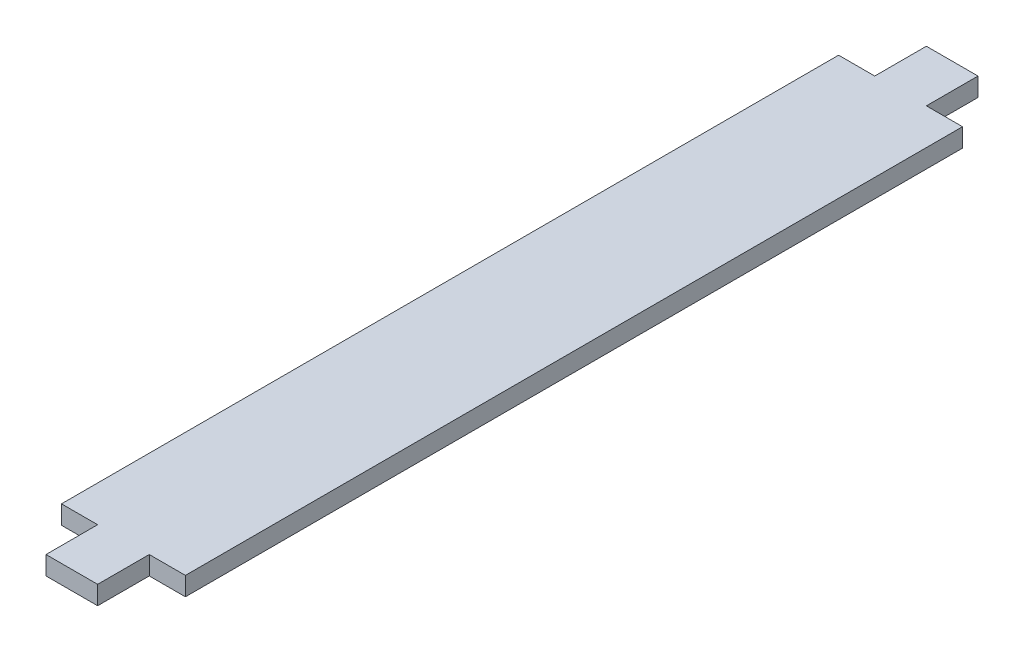
SolidWorks part; units mm, degrees
ref_plane "Front Plane" through (0, 0, 0) normal (0, 0, 1) x (1, 0, 0)
ref_plane "Top Plane" through (0, 0, 0) normal (0, 1, 0) x (1, 0, 0)
ref_plane "Right Plane" through (0, 0, 0) normal (1, 0, 0) x (0, 0, -1)
sketch "Sketch1" plane through (0, 0, 0) normal (0, 1, 0) x (1, 0, 0)
  line L0 (-363.1089, 480) -> (-363.1089, -480)
  line L1 (-363.1089, -480) -> (-303.1089, -480)
  line L2 (-303.1089, -480) -> (-303.1089, -400)
  line L3 (-303.1089, -400) -> (303.1089, -50)
  line L4 (303.1089, -50) -> (1036.8911, -50)
  line L5 (1036.8911, -50) -> (1036.8911, 50) construction
  line L6 (1036.8911, 50) -> (303.1089, 50)
  line L7 (303.1089, 50) -> (-303.1089, 400)
  line L8 (-303.1089, 400) -> (-303.1089, 480)
  line L9 (-303.1089, 480) -> (-363.1089, 480)
  line L10 (-363.1089, 0) -> (1036.8911, 0) construction
  line L11 (0, 225) -> (0, -225) construction
  line L14 (1036.8911, 50) -> (1066.8911, 50)
  line L15 (1036.8911, 50) -> (1036.8911, -50) construction
  line L16 (1036.8911, -50) -> (1066.8911, -50)
  line L17 (1066.8911, 50) -> (1066.8911, -50)
  dimension "D1" = 960
  dimension "D2" = 60
  dimension "D3" = 100
  dimension "D4" = 1400
  dimension "D5" = 150
  dimension "D6" = 80
  dimension "D7" = 30
extrude "Boss-Extrude1" add sketch "Sketch1" along normal blind 9
sketch "Sketch2" plane through (0, 9, 0) normal (0, 1, 0) x (1, 0, 0)
  line L1 (-363.1089, 480) -> (-303.1089, 480)
  line L2 (-363.1089, 480) -> (-363.1089, 400)
  line L3 (-363.1089, 400) -> (-303.1089, 400)
  line L4 (-303.1089, 480) -> (-303.1089, 400)
  line L5 (-363.1089, -480) -> (-303.1089, -480)
  line L6 (-363.1089, -480) -> (-363.1089, -400)
  line L7 (-363.1089, -400) -> (-303.1089, -400)
  line L8 (-303.1089, -480) -> (-303.1089, -400)
extrude "Boss-Extrude2" add sketch "Sketch2" along normal blind 500
sketch "Sketch3" plane through (0, 0, 0) normal (0, 0, 1) x (1, 0, 0)
  line L0 (-333.1089, 509) -> (-333.1089, 254.2) construction
  line L1 (-363.1089, 509) -> (-303.1089, 509) construction
  line L2 (-333.1089, 254.2) -> (-333.1089, 25) construction
  line L3 (-333.1089, 25) -> (-333.1089, 0) construction
  line L4 (-363.1089, 0) -> (-303.1089, 0) construction
  line L6 (-363.1089, 509) -> (-303.1089, 509)
  line L7 (-363.1089, 509) -> (-363.1089, 9)
  line L8 (-363.1089, 9) -> (-303.1089, 9)
  line L9 (-303.1089, 509) -> (-303.1089, 9)
  circle A0 centre (-333.1089, 254.2) radius 229.2
  circle A1 centre (-333.1089, 254.2) radius 6
  circle A2 centre (-333.1089, 254.2) radius 30
  dimension "D1" = 458.4
  dimension "D3" = 12
  dimension "D2" = 25
extrude "Cut-Extrude1" cut sketch "Sketch3" against normal through all both and the other way through all contours A2 L9 A0 L7 | A0 L9 L6 L7 | A1 region at (-333.1089, 495.8654, 0) region at (-333.1089, 380.1444, 0) region at (-333.1089, 254.2, 0)
sketch "Sketch4" plane through (0, 9, 0) normal (0, 1, 0) x (1, 0, 0)
  line L0 (866.8911, 25) -> (1066.8911, 25)
  line L2 (866.8911, -25) -> (1066.8911, -25)
  line L3 (1066.8911, -25) -> (1066.8911, 25)
  line L4 (866.8911, 0) -> (1066.8911, 0) construction
  line L5 (1066.8911, -50) -> (1066.8911, 50) construction
  circle A0 centre (866.8911, 0) radius 25
  dimension "D1" = 50
  dimension "D2" = 200
extrude "Cut-Extrude2" cut sketch "Sketch4" against normal through all contours L4 A0 L2 | A0 L4 L3 L0 | A0 region at (976.6223, 9, -12.7057) region at (884.0688, 9, -17.1777) region at (976.6223, 9, 12.7057)
sketch "Sketch16" plane through (0, 0, 0) normal (0, 0, 1) x (1, 0, 0)
  line L0 (-359.656, 240.2268) -> (-348.1089, 218.2888)
  line L5 (-348.1089, 218.2888) -> (-348.1089, 24)
  line L7 (-363.1089, 9) -> (-288.1089, 9)
  line L8 (303.1089, 9) -> (-303.1089, 9) construction
  line L9 (-303.1089, 254.2) -> (-303.1089, 24)
  line L10 (-348.1089, 24) -> (-363.1089, 9)
  line L11 (-303.1089, 254.2) -> (-303.1089, 9) construction
  line L12 (-303.1089, 24) -> (-288.1089, 9)
  line L13 (-348.1089, 24) -> (-303.1089, 24) construction
  line L14 (-346.3825, 247.2134) -> (-358.4836, 270.2039)
  line L15 (-319.8353, 261.1866) -> (-331.9364, 284.1771)
  circle A0 centre (-333.1089, 254.2) radius 15
  circle A1 centre (-333.1089, 254.2) radius 30
  arc A2 (-303.1089, 254.2) -> (-363.1089, 254.2) centre (-333.1089, 254.2) ccw construction
  circle A3 centre (-360.6089, 215.2) radius 12.5 construction
  dimension "D1" = 30
  dimension "D4" = 25
  dimension "D2" = 45
  dimension "D3" = 45
extrude "Boss-Extrude8" add sketch "Sketch16" along normal blind 305 and the other way blind 305 contours A1 L0 L5 L10 L7 L12 L9 | A1 L15 A0 L14 region at (-325.4564, 117.1914, 0) region at (-362.2383, 255.3393, 0)
sketch "Sketch17" plane through (0, 0, 0) normal (1, 0, 0) x (0, 0, -1)
  line L1 (230, 309) -> (-230, 309)
  line L2 (230, 309) -> (230, 9)
  line L3 (230, 9) -> (-230, 9)
  line L4 (-230, 309) -> (-230, 9)
  line L5 (0, 0) -> (0, 309) construction
  line L6 (480, 0) -> (-480, 0) construction
  dimension "D1" = 460
  dimension "D2" = 9
  dimension "D3" = 300
extrude "Cut-Extrude9" cut sketch "Sketch17" against normal through all
sketch "Sketch7" plane through (0, 0, 0) normal (1, 0, 0) x (0, 0, -1)
  line L1 (480, 284.2) -> (230, 284.2)
  line L2 (480, 284.2) -> (480, 9)
  line L3 (480, 9) -> (230, 9)
  line L4 (230, 284.2) -> (230, 9)
  line L5 (230, 218.2888) -> (230, 24) construction
  line L6 (471, 146.6) -> (444.5, 146.6) construction
  line L7 (480, 284.2) -> (471, 284.2)
  line L8 (480, 284.2) -> (480, 9)
  line L9 (480, 9) -> (471, 9)
  line L10 (471, 284.2) -> (471, 9)
  line L11 (400, 9) -> (409, 9)
  line L12 (400, 9) -> (400, 284.2)
  line L13 (400, 284.2) -> (409, 284.2)
  line L14 (409, 9) -> (409, 284.2)
  line L15 (444.5, 284.2) -> (435.5, 284.2)
  line L16 (444.5, 284.2) -> (444.5, 9)
  line L17 (444.5, 9) -> (435.5, 9)
  line L18 (435.5, 284.2) -> (435.5, 9)
  line L19 (444.5, 146.6) -> (435.5, 146.6) construction
  line L20 (435.5, 146.6) -> (409, 146.6) construction
  line L22 (0, 274.5241) -> (0, -136.9768) construction
  line L23 (-435.5, 146.6) -> (-409, 146.6) construction
  line L24 (305, 284.2) -> (296, 284.2)
  line L25 (305, 284.2) -> (305, 9)
  line L26 (305, 9) -> (296, 9)
  line L27 (296, 284.2) -> (296, 9)
  line L28 (239, 9) -> (230, 9)
  line L29 (239, 9) -> (239, 284.2)
  line L30 (239, 284.2) -> (230, 284.2)
  line L31 (230, 9) -> (230, 284.2)
  line L32 (-444.5, 146.6) -> (-435.5, 146.6) construction
  line L33 (-471, 146.6) -> (-444.5, 146.6) construction
  line L34 (-230, 9) -> (-230, 284.2)
  line L35 (-239, 284.2) -> (-230, 284.2)
  line L36 (-239, 9) -> (-239, 284.2)
  line L37 (-239, 9) -> (-230, 9)
  line L38 (-296, 284.2) -> (-296, 9)
  line L39 (-305, 9) -> (-296, 9)
  line L40 (-305, 284.2) -> (-305, 9)
  line L41 (-305, 284.2) -> (-296, 284.2)
  line L42 (-435.5, 284.2) -> (-435.5, 9)
  line L43 (-444.5, 9) -> (-435.5, 9)
  line L44 (-444.5, 284.2) -> (-444.5, 9)
  line L45 (-444.5, 284.2) -> (-435.5, 284.2)
  line L46 (-409, 9) -> (-409, 284.2)
  line L47 (-400, 284.2) -> (-409, 284.2)
  line L48 (-400, 9) -> (-400, 284.2)
  line L49 (-400, 9) -> (-409, 9)
  line L50 (-471, 284.2) -> (-471, 9)
  line L51 (-480, 9) -> (-471, 9)
  line L52 (-480, 284.2) -> (-480, 9)
  line L53 (-480, 284.2) -> (-471, 284.2)
  line L54 (-230, 284.2) -> (-230, 9)
  line L55 (-480, 9) -> (-230, 9)
  line L56 (-480, 284.2) -> (-480, 9)
  line L57 (-480, 284.2) -> (-230, 284.2)
  line L58 (305, 218.2888) -> (305, 24) construction
  dimension "D1" = 9
  dimension "D2" = 9
  dimension "D3" = 9
  dimension "D4" = 9
  dimension "D5" = 9
extrude "Cut-Extrude4" cut sketch "Sketch7" against normal through all both and the other way through all contours L1 L16 L3 L10 | L18 L1 L14 L3 | L29 L3 L27 L1 | L57 L38 L55 L36 | L57 L42 L55 L46 | L57 L50 L55 L44 | L1 L18 L3 L16 | L45 L44 L43 L42 region at (0, 146.6, -457.75) region at (0, 146.6, -440) region at (0, 146.6, -422.25) region at (0, 146.6, -267.5) region at (0, 146.6, 267.5) region at (0, 146.6, 422.25) region at (0, 146.6, 440) region at (0, 146.6, 457.75)
sketch "Sketch10" plane through (0, 9, 0) normal (0, 1, 0) x (1, 0, 0)
  line L0 (-363.1089, 221) -> (-113.0718, 221)
  line L2 (-113.0718, 221) -> (269.7114, 0)
  line L3 (269.7114, 0) -> (-113.0718, -221)
  line L4 (-113.0718, -221) -> (-363.1089, -221)
  line L5 (-363.1089, -221) -> (-363.1089, 221)
  line L6 (0, 0) -> (269.7114, 0) construction
  line L7 (-363.1089, 0) -> (0, 0) construction
  line L8 (-113.0718, -221) -> (-113.0718, 221) construction
  line L9 (303.1089, 50) -> (-303.1089, 400) construction
  line L10 (-363.1089, -230) -> (-363.1089, 230) construction
  line L11 (303.1089, 50) -> (337.7499, 30)
  line L12 (337.7499, 30) -> (806.8911, 30)
  line L13 (806.8911, 30) -> (841.5321, 50)
  line L14 (1066.8911, 50) -> (303.1089, 50) construction
  line L15 (841.5321, 50) -> (303.1089, 50)
  line L16 (303.1089, -50) -> (337.7499, -30)
  line L17 (337.7499, -30) -> (806.8911, -30)
  line L18 (806.8911, -30) -> (841.5321, -50)
  line L19 (303.1089, -50) -> (1066.8911, -50) construction
  line L20 (841.5321, -50) -> (303.1089, -50)
  line L21 (337.7499, -30) -> (337.7499, 30) construction
  line L22 (269.7114, 0) -> (337.7499, 0) construction
  line L23 (806.8911, 30) -> (806.8911, -30) construction
  line L24 (-303.1089, -400) -> (303.1089, -50) construction
  line L25 (841.5321, 50) -> (841.5321, -50) construction
  line L27 (-363.1089, 230) -> (-288.1089, 230) construction
  line L28 (-363.1089, -230) -> (-288.1089, -230) construction
  arc A0 (866.8911, 25) -> (866.8911, -25) centre (866.8911, 0) ccw construction
  dimension "D1" = 60
  dimension "D2" = 30
  dimension "D3" = 60
  dimension "D4" = 60
  dimension "D5" = 9
  dimension "D6" = 9
extrude "Cut-Extrude6" cut sketch "Sketch10" against normal through all
sketch "Sketch11" plane through (-363.1089, 0, 0) normal (-1, 0, 0) x (0, 0, 1)
  line L0 (-480, 254.2) -> (-480, 0) construction
  line L1 (-480, 224.2) -> (-400, 224.2)
  line L2 (-480, 224.2) -> (-480, 215.2)
  line L3 (-480, 215.2) -> (-400, 215.2)
  line L4 (-400, 224.2) -> (-400, 215.2)
  line L5 (-400, 254.2) -> (-400, 9) construction
  line L6 (400, 254.2) -> (400, 9) construction
  line L7 (400, 224.2) -> (480, 224.2)
  line L8 (400, 224.2) -> (400, 215.2)
  line L9 (400, 215.2) -> (480, 215.2)
  line L10 (480, 224.2) -> (480, 215.2)
  line L11 (480, 254.2) -> (480, 0) construction
  line L12 (-400, 224.2) -> (400, 224.2) construction
  line L13 (400, 215.2) -> (-400, 215.2) construction
  line L14 (-400, 284.2) -> (-409, 284.2) construction
  dimension "D1" = 9
  dimension "D2" = 60
extrude "Boss-Extrude5" add sketch "Sketch11" against normal up to surface (60 mm away) up to face at (-303.1089, 115.9778, 435.5556)
sketch "Sketch18" plane through (-348.1089, 0, 0) normal (-1, 0, 0) x (0, 0, 1)
  line L0 (-230, 218.2888) -> (-230, 24) construction
  line L1 (-305, 218.2888) -> (-230, 218.2888)
  line L2 (-305, 218.2888) -> (-305, 209.2888)
  line L3 (-305, 209.2888) -> (-230, 209.2888)
  line L4 (-230, 218.2888) -> (-230, 209.2888)
  line L5 (230, 24) -> (230, 218.2888) construction
  line L6 (305, 218.2888) -> (230, 218.2888)
  line L7 (305, 218.2888) -> (305, 209.2888)
  line L8 (305, 209.2888) -> (230, 209.2888)
  line L9 (230, 218.2888) -> (230, 209.2888)
  dimension "D1" = 9
  dimension "D2" = 9
extrude "Boss-Extrude9" add sketch "Sketch18" against normal up to surface (45 mm away) up to face at (-303.1089, 139.1, -234.5)
sketch "Sketch12" plane through (0, 9, 0) normal (0, 1, 0) x (1, 0, 0)
  line L0 (-363.1089, -480) -> (-303.1089, -480) construction
  line L1 (-363.1089, 480) -> (-303.1089, 480)
  line L2 (-363.1089, 480) -> (-363.1089, 489)
  line L3 (-363.1089, 489) -> (-303.1089, 489)
  line L4 (-303.1089, 480) -> (-303.1089, 489)
  line L5 (-363.1089, -480) -> (-303.1089, -480)
  line L6 (-363.1089, -480) -> (-363.1089, -489)
  line L7 (-363.1089, -489) -> (-303.1089, -489)
  line L8 (-303.1089, -480) -> (-303.1089, -489)
  dimension "D1" = 9
  dimension "D2" = 9
extrude "Boss-Extrude6" add sketch "Sketch12" against normal blind 9
fillet "Fillet3" radius 9 27 edges at (-303.1089, 4.5, -489) (-363.1089, 4.5, -489) (-363.1089, 4.5, -221) (-363.1089, 4.5, 221) (-363.1089, 4.5, 489) (-303.1089, 4.5, 489) (841.5321, 4.5, 50) (806.8911, 4.5, 30) (841.5321, 4.5, -50) (806.8911, 4.5, -30) (337.7499, 4.5, -30) (337.7499, 4.5, 30) (269.7114, 4.5, 0) (-113.0718, 4.5, 221) (-113.0718, 4.5, -221) (-303.1089, 24, -234.5) (-303.1089, 24, -300.5) (-303.1089, 24, 234.5) (-303.1089, 24, 300.5) (-348.1089, 24, 234.5) (-348.1089, 24, 300.5) (-348.1089, 24, -234.5) (-348.1089, 24, -300.5) (1066.8911, 4.5, 50) (1066.8911, 4.5, 25) (1066.8911, 4.5, -25) (1066.8911, 4.5, -50)
sketch "Sketch15" plane through (0, 9, 0) normal (0, 1, 0) x (1, 0, 0)
  line L0 (-83.154, 230) -> (-83.154, -230)
  line L1 (-113.154, 230) -> (-113.154, 220.6933) construction
  line L2 (-363.1089, 230) -> (-288.1089, 230) construction
  line L4 (-83.154, -230) -> (-143.154, -230)
  line L5 (-143.154, -230) -> (-143.154, 230)
  line L6 (-143.154, 230) -> (-83.154, 230)
  line L7 (0, 0) -> (-83.154, 0) construction
  arc A0 (-110.9833, 219.7942) -> (-115.4833, 221) centre (-115.4833, 212) ccw construction
  dimension "D1" = 60
extrude "Boss-Extrude7" add sketch "Sketch15" against normal blind 9
fillet "Fillet4" radius 9 4 edges at (-83.154, 4.5, -203.7269) (-83.154, 4.5, 203.7269) (-143.154, 4.5, 221) (-143.154, 4.5, -221)
sketch "Sketch20" plane through (0, 9, 0) normal (0, 1, 0) x (1, 0, 0)
  line L0 (-348.1089, 480) -> (-348.1089, 400)
  line L1 (-363.1089, 480) -> (-303.1089, 480)
  line L2 (-363.1089, 480) -> (-363.1089, 471)
  line L3 (-363.1089, 471) -> (-303.1089, 471)
  line L4 (-303.1089, 480) -> (-303.1089, 471)
  line L5 (-363.1089, 409) -> (-303.1089, 409)
  line L6 (-363.1089, 409) -> (-363.1089, 400)
  line L7 (-363.1089, 400) -> (-303.1089, 400)
  line L8 (-303.1089, 409) -> (-303.1089, 400)
  line L9 (-363.1089, 305) -> (-288.1089, 305)
  line L10 (-363.1089, 305) -> (-363.1089, 296)
  line L11 (-363.1089, 296) -> (-288.1089, 296)
  line L12 (-288.1089, 305) -> (-288.1089, 296)
  line L13 (-363.1089, 239) -> (-288.1089, 239)
  line L14 (-363.1089, 239) -> (-363.1089, 230)
  line L15 (-363.1089, 230) -> (-288.1089, 230)
  line L16 (-288.1089, 239) -> (-288.1089, 230)
  line L17 (-318.1089, 480) -> (-318.1089, 400)
  line L18 (-363.1089, 440) -> (-348.1089, 440) construction
  line L19 (-363.1089, 409) -> (-363.1089, 471) construction
  line L20 (-348.1089, 440) -> (-318.1089, 440) construction
  line L21 (-318.1089, 440) -> (-303.1089, 440) construction
  line L22 (-303.1089, 471) -> (-303.1089, 409) construction
  line L23 (-340.6089, 305) -> (-340.6089, 230)
  line L24 (-310.6089, 305) -> (-310.6089, 230)
  line L25 (-288.1089, 296) -> (-288.1089, 239) construction
  line L26 (-363.1089, 267.5) -> (-340.6089, 267.5) construction
  line L27 (-363.1089, 296) -> (-363.1089, 239) construction
  line L28 (-340.6089, 267.5) -> (-310.6089, 267.5) construction
  line L29 (-310.6089, 267.5) -> (-288.1089, 267.5) construction
  line L30 (-512.4702, 0) -> (462.9433, 0) construction
  line L31 (-310.6089, -267.5) -> (-288.1089, -267.5) construction
  line L32 (-340.6089, -267.5) -> (-310.6089, -267.5) construction
  line L33 (-363.1089, -267.5) -> (-340.6089, -267.5) construction
  line L34 (-288.1089, -296) -> (-288.1089, -239) construction
  line L35 (-318.1089, -440) -> (-303.1089, -440) construction
  line L36 (-348.1089, -440) -> (-318.1089, -440) construction
  line L37 (-363.1089, -440) -> (-348.1089, -440) construction
  line L38 (-310.6089, -305) -> (-310.6089, -230)
  line L39 (-340.6089, -305) -> (-340.6089, -230)
  line L40 (-318.1089, -480) -> (-318.1089, -400)
  line L41 (-288.1089, -239) -> (-288.1089, -230)
  line L42 (-363.1089, -230) -> (-288.1089, -230)
  line L43 (-363.1089, -239) -> (-363.1089, -230)
  line L44 (-363.1089, -239) -> (-288.1089, -239)
  line L45 (-288.1089, -305) -> (-288.1089, -296)
  line L46 (-363.1089, -296) -> (-288.1089, -296)
  line L47 (-363.1089, -305) -> (-363.1089, -296)
  line L48 (-363.1089, -305) -> (-288.1089, -305)
  line L49 (-303.1089, -409) -> (-303.1089, -400)
  line L50 (-363.1089, -400) -> (-303.1089, -400)
  line L51 (-363.1089, -409) -> (-363.1089, -400)
  line L52 (-363.1089, -409) -> (-303.1089, -409)
  line L53 (-303.1089, -480) -> (-303.1089, -471)
  line L54 (-363.1089, -471) -> (-303.1089, -471)
  line L55 (-363.1089, -480) -> (-363.1089, -471)
  line L56 (-363.1089, -480) -> (-303.1089, -480)
  line L57 (-348.1089, -480) -> (-348.1089, -400)
  dimension "D1" = 30
  dimension "D2" = 30
sketch "Sketch21" plane through (0, 9, 0) normal (0, 1, 0) x (1, 0, 0)
  line L0 (1066.8911, 34) -> (1066.8911, 41) construction
  line L1 (-363.1089, 489) -> (1066.8911, 489)
  line L2 (-363.1089, 489) -> (-363.1089, -489)
  line L3 (-363.1089, -489) -> (1066.8911, -489)
  line L4 (1066.8911, 489) -> (1066.8911, -489)
  line L5 (-354.1089, -489) -> (-312.1089, -489) construction
  line L6 (-363.1089, -305) -> (-363.1089, -400) construction
  line L7 (-312.1089, 489) -> (-354.1089, 489) construction
extrude "Cut-Extrude11" cut sketch "Sketch20" against normal through all both and the other way through all contours L56 L57 L54 L55 | L40 L56 L53 L54 | L52 L57 L50 L51 | L40 L52 L49 L50 | L47 L48 L39 L46 | L38 L48 L45 L46 | L38 L44 L41 L42 | L43 L44 L39 L42 | L23 L13 L14 L15 | L13 L24 L15 L16 | L9 L24 L11 L12 | L23 L9 L10 L11 | L6 L7 L0 L5 | L5 L17 L7 L8 | L1 L17 L3 L4 | L2 L3 L0 L1 region at (-355.6089, 9, -475.5) region at (-310.6089, 9, -475.5) region at (-355.6089, 9, -404.5) region at (-310.6089, 9, -404.5) region at (-351.8589, 9, -300.5) region at (-299.3589, 9, -300.5) region at (-351.8589, 9, -234.5) region at (-299.3589, 9, -234.5) region at (-299.3589, 9, 300.5) region at (-351.8589, 9, 300.5) region at (-299.3589, 9, 234.5) region at (-351.8589, 9, 234.5) region at (-310.6089, 9, 475.5) region at (-355.6089, 9, 475.5) region at (-310.6089, 9, 404.5) region at (-355.6089, 9, 404.5)
extrude "Cut-Extrude12" cut sketch "Sketch21" along normal through all
sketch "Sketch22" plane through (0, 9, 0) normal (0, 1, 0) x (1, 0, 0)
  line L0 (1066.8911, 34) -> (1066.8911, 41) construction
  line L1 (-363.1089, -489) -> (1066.8911, -489)
  line L2 (-363.1089, -489) -> (-363.1089, 489)
  line L3 (-363.1089, 489) -> (1066.8911, 489)
  line L4 (1066.8911, -489) -> (1066.8911, 489)
  line L5 (-312.1089, 489) -> (-354.1089, 489) construction
  line L6 (-363.1089, 471) -> (-363.1089, 409) construction
  line L7 (-354.1089, -489) -> (-312.1089, -489) construction
  line L8 (-83.154, 188.1385) -> (-143.154, 188.1385)
  line L9 (-143.154, 212) -> (-143.154, -212) construction
  line L10 (-113.154, 188.1385) -> (-113.154, 213.1385) construction
  line L11 (-69.654, 195.9327) -> (-69.654, 265.2147)
  line L12 (-125.654, 188.1385) -> (-100.654, 188.1385)
  line L13 (256.2114, 7.7942) -> (286.2114, 59.7558)
  line L14 (256.2114, 7.7942) -> (231.2114, 22.228)
  line L15 (231.2114, 22.228) -> (239.9614, 37.3834)
  line L16 (335.6615, 31.2058) -> (-303.1089, 400) construction
  line L17 (256.2114, 7.7942) -> (256.2114, -7.7942)
  line L18 (-69.654, 265.2147) -> (-297.5196, 489)
  line L19 (-143.154, 188.1385) -> (-363.1089, 188.1385)
  line L20 (340.1615, 88.1184) -> (-69.654, 265.2147)
  line L21 (340.1615, 88.1184) -> (1066.8911, 88.1184)
  line L22 (194.4241, 7.7942) -> (-83.154, 188.1385)
  line L23 (-69.654, 195.9327) -> (-83.154, 188.1385)
  line L24 (-125.654, 188.1385) -> (-125.654, 213.1385)
  line L25 (-125.654, 213.1385) -> (-100.654, 213.1385)
  line L26 (-100.654, 188.1385) -> (-100.654, 213.1385)
  line L27 (-69.654, 195.9327) -> (-44.654, 181.4989)
  line L28 (256.2114, 7.7942) -> (-69.654, 195.9327) construction
  line L29 (-44.654, 181.4989) -> (-44.654, 203.64)
  line L30 (-44.654, 203.64) -> (-69.654, 218.0737)
  line L32 (-69.654, 265.2147) -> (-44.654, 250.781)
  line L33 (-44.654, 250.781) -> (-44.654, 228.64)
  line L34 (-44.654, 228.64) -> (-69.654, 243.0737)
  line L35 (-44.654, 203.64) -> (-44.654, 228.64)
  line L36 (239.9614, 37.3834) -> (264.9614, 22.9497)
  line L37 (239.9614, 37.3834) -> (252.4614, 59.0341)
  line L38 (252.4614, 59.0341) -> (277.4614, 44.6003)
  line L39 (252.4614, 59.0341) -> (261.2114, 74.1895)
  line L40 (261.2114, 74.1895) -> (286.2114, 59.7558)
  line L41 (194.4241, 7.7942) -> (256.2114, 7.7942)
  line L42 (286.2114, 59.7558) -> (340.1615, 88.1184)
  line L43 (-181.378, 0) -> (-33.8367, 0) construction
  line L44 (-113.154, -188.1385) -> (-113.154, -213.1385) construction
  line L45 (286.2114, -59.7558) -> (340.1615, -88.1184)
  line L46 (194.4241, -7.7942) -> (256.2114, -7.7942)
  line L47 (261.2114, -74.1895) -> (286.2114, -59.7558)
  line L48 (252.4614, -59.0341) -> (261.2114, -74.1895)
  line L49 (252.4614, -59.0341) -> (277.4614, -44.6003)
  line L50 (239.9614, -37.3834) -> (252.4614, -59.0341)
  line L51 (239.9614, -37.3834) -> (264.9614, -22.9497)
  line L52 (-44.654, -203.64) -> (-44.654, -228.64)
  line L53 (-44.654, -228.64) -> (-69.654, -243.0737)
  line L54 (-44.654, -250.781) -> (-44.654, -228.64)
  line L55 (-69.654, -265.2147) -> (-44.654, -250.781)
  line L56 (-44.654, -203.64) -> (-69.654, -218.0737)
  line L57 (-44.654, -181.4989) -> (-44.654, -203.64)
  line L58 (-69.654, -195.9327) -> (-44.654, -181.4989)
  line L59 (-100.654, -188.1385) -> (-100.654, -213.1385)
  line L60 (-125.654, -213.1385) -> (-100.654, -213.1385)
  line L61 (-125.654, -188.1385) -> (-125.654, -213.1385)
  line L62 (-69.654, -195.9327) -> (-83.154, -188.1385)
  line L63 (194.4241, -7.7942) -> (-83.154, -188.1385)
  line L64 (340.1615, -88.1184) -> (1066.8911, -88.1184)
  line L65 (340.1615, -88.1184) -> (-69.654, -265.2147)
  line L66 (-143.154, -188.1385) -> (-363.1089, -188.1385)
  line L67 (-69.654, -265.2147) -> (-297.5196, -489)
  line L68 (231.2114, -22.228) -> (239.9614, -37.3834)
  line L69 (256.2114, -7.7942) -> (231.2114, -22.228)
  line L70 (256.2114, -7.7942) -> (286.2114, -59.7558)
  line L71 (-125.654, -188.1385) -> (-100.654, -188.1385)
  line L72 (-69.654, -195.9327) -> (-69.654, -265.2147)
  line L73 (-83.154, -188.1385) -> (-143.154, -188.1385)
  line L74 (-363.1089, -489) -> (1066.8911, -489)
  line L75 (194.4241, -7.7942) -> (194.4241, 7.7942)
  dimension "D1" = 25
  dimension "D2" = 25
  dimension "D3" = 25
  dimension "D4" = 25
  dimension "D5" = 25
  dimension "D6" = 25
extrude "Cut-Extrude13" cut sketch "Sketch22" against normal through all contours L26 L8 L23 L11 L18 L3 L2 L19 L24 L25 | L29 L30 L11 L27 | L34 L33 L32 L11 | L62 L73 L59 L60 L61 L66 L2 L1 L67 L72 | L58 L72 L56 L57 | L53 L72 L55 L54 region at (-246.5905, 9, 308.954) region at (-57.154, 9, 246.9274) region at (-246.5905, 9, -308.954) region at (-57.154, 9, 199.7863) region at (-57.154, 9, -246.9274) region at (-57.154, 9, -199.7863)
